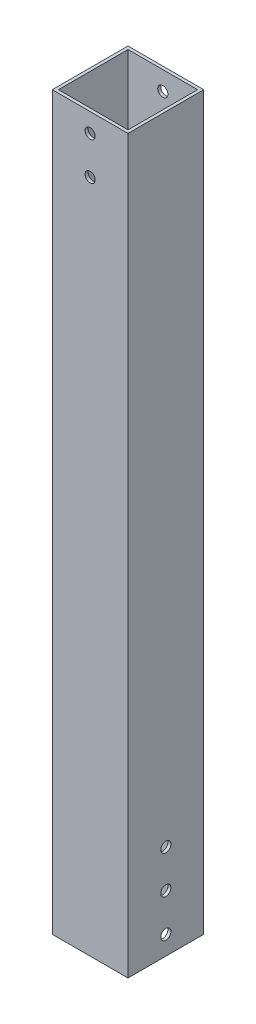
SolidWorks part; units mm, degrees
material "6061 Alloy"
ref_plane "Front Plane" through (0, 0, 0) normal (0, 0, 1) x (1, 0, 0)
ref_plane "Top Plane" through (0, 0, 0) normal (0, 1, 0) x (1, 0, 0)
ref_plane "Right Plane" through (0, 0, 0) normal (1, 0, 0) x (0, 0, -1)
sketch "Sketch1" plane through (0, 0, 0) normal (0, 1, 0) x (1, 0, 0)
  line L1 (19.05, 19.05) -> (-19.05, 19.05)
  line L2 (19.05, 19.05) -> (19.05, -19.05)
  line L3 (19.05, -19.05) -> (-19.05, -19.05)
  line L4 (-19.05, 19.05) -> (-19.05, -19.05)
  line L5 (19.05, 19.05) -> (-19.05, -19.05) construction
  line L6 (19.05, -19.05) -> (-19.05, 19.05) construction
  point P0 (0, 0)
  dimension "D1" = 38.1
extrude "Extrude-Thin1" add sketch "Sketch1" along normal blind 368.3 thin thin type one direction reverse wall 1.524
sketch "Sketch2" plane through (19.05, 0, 0) normal (1, 0, 0) x (0, 0, -1)
  line L0 (-19.05, 0) -> (19.05, 0) construction
  circle A0 centre (0, 9.525) radius 2.54
  circle A1 centre (0, 28.575) radius 2.54
  circle A2 centre (0, 47.625) radius 2.54
  dimension "D1" = 5.08
  dimension "D4" = 19.05
  dimension "D2" = 9.525
  dimension "D3" = 28.575
hole_wizard "#10 Clearance Hole1" positions "Sketch3" profile "Sketch4" hole size "#10" standard "ANSI Inch" end condition through all
sketch "Sketch3" plane through (19.05, 0, 0) normal (1, 0, 0) x (0, 0, -1)
  point P0 (0, 9.525)
  point P3 (0, 28.575)
  point P6 (0, 47.625)
sketch "Sketch4" plane through (19.05, 9.525, 0) normal (0, 1, 0) x (0, 0, -1)
  line L0 (0, 0) -> (0, 38.1)
  line L1 (0, 38.1) -> (2.5527, 38.1)
  line L2 (2.5527, 38.1) -> (2.5527, 0)
  line L5 (2.5527, 0) -> (0, 0)
  line L11 (0, -6.35) -> (0, 107.95) construction
  dimension "Thru Hole Dia." = 5.1054
  dimension "Thru Hole Depth" = 38.1
sketch "Sketch5" plane through (0, 0, 19.05) normal (0, 0, 1) x (1, 0, 0)
  line L0 (-19.05, 368.3) -> (19.05, 368.3) construction
  circle A0 centre (0, 358.775) radius 2.54
  circle A1 centre (0, 339.725) radius 2.54
  dimension "D1" = 5.08
  dimension "D2" = 9.525
  dimension "D3" = 28.575
hole_wizard "#10 Clearance Hole2" positions "Sketch6" profile "Sketch7" hole size "#10" standard "ANSI Inch" end condition through all
sketch "Sketch6" plane through (0, 0, 19.05) normal (0, 0, 1) x (1, 0, 0)
  point P0 (0, 339.725)
  point P3 (0, 358.775)
sketch "Sketch7" plane through (0, 339.725, 19.05) normal (1, 0, 0) x (0, -1, 0)
  line L0 (0, 0) -> (0, 38.1)
  line L1 (0, 38.1) -> (2.5527, 38.1)
  line L2 (2.5527, 38.1) -> (2.5527, 0)
  line L5 (2.5527, 0) -> (0, 0)
  line L11 (0, -6.35) -> (0, 107.95) construction
  dimension "Thru Hole Dia." = 5.1054
  dimension "Thru Hole Depth" = 38.1
sketch "Sketch8" plane through (19.05, 0, 0) normal (1, 0, 0) x (0, 0, -1)
  line L0 (-19.05, 59.7027) -> (19.05, 59.7027) construction
  line L1 (-19.05, 368.3) -> (-19.05, 0) construction
  line L2 (19.05, 368.3) -> (19.05, 0) construction
  line L3 (17.526, 368.3) -> (-17.526, 368.3) construction
  line L4 (-7.7094, 328.6285) -> (6.35, 328.6285) construction
  line L5 (-3.175, 328.6285) -> (3.175, 328.6285)
  line L6 (6.35, 325.4535) -> (6.35, 308.007)
  line L7 (0.1915, 306.9211) -> (-6.1585, 324.3676)
  line L8 (-3.175, 331.8035) -> (3.175, 331.8035)
  line L9 (-6.35, 334.9785) -> (-6.35, 352.425)
  line L10 (-0.1915, 353.5109) -> (6.1585, 336.0644)
  line L11 (-0.1915, 301.9934) -> (6.1585, 284.547)
  line L12 (-6.35, 368.3) -> (-6.35, 0) construction
  line L13 (-19.05, 368.3) -> (19.05, 368.3) construction
  line L14 (-19.05, 0) -> (19.05, 0) construction
  line L15 (6.35, 0) -> (6.35, 368.3) construction
  line L16 (-19.05, 348.6497) -> (-6.35, 348.6497) construction
  line L17 (6.35, 348.6497) -> (19.05, 348.6497) construction
  line L18 (-6.35, 283.461) -> (-6.35, 300.9075)
  line L19 (-3.175, 280.286) -> (3.175, 280.286)
  line L20 (-3.175, 277.111) -> (3.175, 277.111)
  line L21 (0.1915, 255.4036) -> (-6.1585, 272.8501)
  line L22 (6.35, 273.936) -> (6.35, 256.4896)
  line L23 (-0.1915, 250.476) -> (6.1585, 233.0295)
  line L24 (-6.35, 231.9436) -> (-6.35, 249.39)
  line L25 (-3.175, 228.7686) -> (3.175, 228.7686)
  line L26 (-3.175, 225.5936) -> (3.175, 225.5936)
  line L27 (0.1915, 203.8862) -> (-6.1585, 221.3326)
  line L28 (6.35, 222.4186) -> (6.35, 204.9721)
  line L29 (-0.1915, 198.9585) -> (6.1585, 181.512)
  line L30 (-6.35, 180.4261) -> (-6.35, 197.8726)
  line L31 (-3.175, 177.2511) -> (3.175, 177.2511)
  line L32 (-3.175, 174.0761) -> (3.175, 174.0761)
  line L33 (0.1915, 152.3687) -> (-6.1585, 169.8152)
  line L34 (6.35, 170.9011) -> (6.35, 153.4546)
  line L35 (-0.1915, 147.441) -> (6.1585, 129.9945)
  line L36 (-6.35, 128.9086) -> (-6.35, 146.3551)
  line L37 (-3.175, 125.7336) -> (3.175, 125.7336)
  line L38 (-3.175, 122.5586) -> (3.175, 122.5586)
  line L39 (0.1915, 100.8512) -> (-6.1585, 118.2977)
  line L40 (6.35, 119.3836) -> (6.35, 101.9371)
  line L41 (-0.1915, 95.9235) -> (6.1585, 78.477)
  line L42 (-6.35, 77.3911) -> (-6.35, 94.8376)
  line L43 (-3.175, 74.2161) -> (3.175, 74.2161)
  line L47 (6.35, 67.8661) -> (6.35, 50.4196) [skipped]
  line L48 (0.1915, 49.3337) -> (-6.1585, 66.7802) [skipped]
  line L49 (-3.175, 71.0411) -> (3.175, 71.0411) [skipped]
  circle A0 centre (0, 47.625) radius 2.5527 construction
  arc A1 (-6.1585, 324.3676) -> (-3.175, 328.6285) centre (-3.175, 325.4535) cw
  arc A2 (3.175, 328.6285) -> (6.35, 325.4535) centre (3.175, 325.4535) cw
  arc A3 (6.35, 308.007) -> (0.1915, 306.9211) centre (3.175, 308.007) cw
  arc A4 (6.1585, 336.0644) -> (3.175, 331.8035) centre (3.175, 334.9785) cw
  arc A5 (-6.35, 352.425) -> (-0.1915, 353.5109) centre (-3.175, 352.425) cw
  arc A6 (-6.35, 334.9785) -> (-3.175, 331.8035) centre (-3.175, 334.9785) ccw
  arc A7 (-6.35, 300.9075) -> (-0.1915, 301.9934) centre (-3.175, 300.9075) cw
  arc A8 (-6.35, 283.461) -> (-3.175, 280.286) centre (-3.175, 283.461) ccw
  arc A9 (6.1585, 284.547) -> (3.175, 280.286) centre (3.175, 283.461) cw
  arc A10 (-6.1585, 272.8501) -> (-3.175, 277.111) centre (-3.175, 273.936) cw
  arc A11 (6.35, 256.4896) -> (0.1915, 255.4036) centre (3.175, 256.4896) cw
  arc A12 (3.175, 277.111) -> (6.35, 273.936) centre (3.175, 273.936) cw
  arc A13 (-6.35, 249.39) -> (-0.1915, 250.476) centre (-3.175, 249.39) cw
  arc A14 (-6.35, 231.9436) -> (-3.175, 228.7686) centre (-3.175, 231.9436) ccw
  arc A15 (6.1585, 233.0295) -> (3.175, 228.7686) centre (3.175, 231.9436) cw
  arc A16 (-6.1585, 221.3326) -> (-3.175, 225.5936) centre (-3.175, 222.4186) cw
  arc A17 (6.35, 204.9721) -> (0.1915, 203.8862) centre (3.175, 204.9721) cw
  arc A18 (3.175, 225.5936) -> (6.35, 222.4186) centre (3.175, 222.4186) cw
  arc A19 (-6.35, 197.8726) -> (-0.1915, 198.9585) centre (-3.175, 197.8726) cw
  arc A20 (-6.35, 180.4261) -> (-3.175, 177.2511) centre (-3.175, 180.4261) ccw
  arc A21 (6.1585, 181.512) -> (3.175, 177.2511) centre (3.175, 180.4261) cw
  arc A22 (-6.1585, 169.8152) -> (-3.175, 174.0761) centre (-3.175, 170.9011) cw
  arc A23 (6.35, 153.4546) -> (0.1915, 152.3687) centre (3.175, 153.4546) cw
  arc A24 (3.175, 174.0761) -> (6.35, 170.9011) centre (3.175, 170.9011) cw
  arc A25 (-6.35, 146.3551) -> (-0.1915, 147.441) centre (-3.175, 146.3551) cw
  arc A26 (-6.35, 128.9086) -> (-3.175, 125.7336) centre (-3.175, 128.9086) ccw
  arc A27 (6.1585, 129.9945) -> (3.175, 125.7336) centre (3.175, 128.9086) cw
  arc A28 (-6.1585, 118.2977) -> (-3.175, 122.5586) centre (-3.175, 119.3836) cw
  arc A29 (6.35, 101.9371) -> (0.1915, 100.8512) centre (3.175, 101.9371) cw
  arc A30 (3.175, 122.5586) -> (6.35, 119.3836) centre (3.175, 119.3836) cw
  arc A31 (-6.35, 94.8376) -> (-0.1915, 95.9235) centre (-3.175, 94.8376) cw
  arc A32 (-6.35, 77.3911) -> (-3.175, 74.2161) centre (-3.175, 77.3911) ccw
  arc A33 (6.1585, 78.477) -> (3.175, 74.2161) centre (3.175, 77.3911) cw
  arc A37 (6.35, 50.4196) -> (0.1915, 49.3337) centre (3.175, 50.4196) cw [skipped]
  arc A38 (3.175, 71.0411) -> (6.35, 67.8661) centre (3.175, 67.8661) cw [skipped]
  arc A39 (-6.1585, 66.7802) -> (-3.175, 71.0411) centre (-3.175, 67.8661) cw [skipped]
  dimension "D1" = 9.525
  dimension "D3" = 3.175
  dimension "D5" = 15.875
  dimension "D8" = 3.175
  dimension "D2" = 20
  dimension "D4" = 12.7
  dimension "D6" = 3.175
  dimension "D7" = 6
extrude "Cut-Extrude1" [suppressed] cut sketch "Sketch8" against normal through all
sketch "Sketch9" plane through (0, 0, 19.05) normal (0, 0, 1) x (1, 0, 0)
  line L0 (-7.7094, 330.2) -> (6.35, 330.2) construction
  line L1 (-3.175, 330.2) -> (3.175, 330.2)
  line L2 (6.35, 327.025) -> (6.35, 309.5785)
  line L3 (0.1915, 308.4926) -> (-6.1585, 325.9391)
  line L4 (-3.175, 281.8575) -> (3.175, 281.8575)
  line L5 (-6.35, 285.0325) -> (-6.35, 302.479)
  line L6 (-0.1915, 303.5649) -> (6.1585, 286.1184)
  line L7 (-3.175, 278.6825) -> (3.175, 278.6825)
  line L8 (-6.35, 368.3) -> (-6.35, 0) construction
  line L9 (-19.05, 368.3) -> (19.05, 368.3) construction
  line L10 (-19.05, 0) -> (19.05, 0) construction
  line L11 (6.35, 0) -> (6.35, 368.3) construction
  line L12 (-19.05, 360.2771) -> (-6.35, 360.2771) construction
  line L13 (-19.05, 368.3) -> (-19.05, 0) construction
  line L14 (6.35, 360.2771) -> (19.05, 360.2771) construction
  line L15 (19.05, 368.3) -> (19.05, 0) construction
  line L16 (0.1915, 256.9751) -> (-6.1585, 274.4216)
  line L17 (6.35, 275.5075) -> (6.35, 258.061)
  line L18 (-6.35, 233.515) -> (-6.35, 250.9615)
  line L19 (-0.1915, 252.0474) -> (6.1585, 234.601)
  line L20 (-3.175, 230.34) -> (3.175, 230.34)
  line L21 (-3.175, 227.165) -> (3.175, 227.165)
  line L22 (0.1915, 205.4576) -> (-6.1585, 222.9041)
  line L23 (6.35, 223.99) -> (6.35, 206.5436)
  line L24 (-6.35, 181.9976) -> (-6.35, 199.444)
  line L25 (-0.1915, 200.53) -> (6.1585, 183.0835)
  line L26 (-3.175, 178.8226) -> (3.175, 178.8226)
  line L27 (-3.175, 175.6476) -> (3.175, 175.6476)
  line L28 (0.1915, 153.9402) -> (-6.1585, 171.3866)
  line L29 (6.35, 172.4726) -> (6.35, 155.0261)
  line L30 (-6.35, 130.4801) -> (-6.35, 147.9266)
  line L31 (-0.1915, 149.0125) -> (6.1585, 131.566)
  line L32 (-3.175, 127.3051) -> (3.175, 127.3051)
  line L33 (-3.175, 124.1301) -> (3.175, 124.1301)
  line L34 (0.1915, 102.4227) -> (-6.1585, 119.8692)
  line L35 (6.35, 120.9551) -> (6.35, 103.5086)
  line L36 (-6.35, 78.9626) -> (-6.35, 96.4091)
  line L37 (-0.1915, 97.495) -> (6.1585, 80.0485)
  line L38 (-3.175, 75.7876) -> (3.175, 75.7876)
  line L39 (-3.175, 72.6126) -> (3.175, 72.6126)
  line L40 (0.1915, 50.9052) -> (-6.1585, 68.3517)
  line L41 (6.35, 69.4376) -> (6.35, 51.9911)
  line L42 (-6.35, 27.4451) -> (-6.35, 44.8916)
  line L43 (-0.1915, 45.9775) -> (6.1585, 28.531)
  line L44 (-3.175, 24.2701) -> (3.175, 24.2701)
  arc A0 (-6.1585, 325.9391) -> (-3.175, 330.2) centre (-3.175, 327.025) cw
  arc A1 (3.175, 330.2) -> (6.35, 327.025) centre (3.175, 327.025) cw
  arc A2 (6.35, 309.5785) -> (0.1915, 308.4926) centre (3.175, 309.5785) cw
  arc A3 (6.1585, 286.1184) -> (3.175, 281.8575) centre (3.175, 285.0325) cw
  arc A4 (-6.35, 302.479) -> (-0.1915, 303.5649) centre (-3.175, 302.479) cw
  arc A5 (-6.35, 285.0325) -> (-3.175, 281.8575) centre (-3.175, 285.0325) ccw
  circle A6 centre (0, 339.725) radius 2.5527 construction
  arc A7 (-6.1585, 274.4216) -> (-3.175, 278.6825) centre (-3.175, 275.5075) cw
  arc A8 (3.175, 278.6825) -> (6.35, 275.5075) centre (3.175, 275.5075) cw
  arc A9 (6.35, 258.061) -> (0.1915, 256.9751) centre (3.175, 258.061) cw
  arc A10 (-6.35, 250.9615) -> (-0.1915, 252.0474) centre (-3.175, 250.9615) cw
  arc A11 (6.1585, 234.601) -> (3.175, 230.34) centre (3.175, 233.515) cw
  arc A12 (-6.35, 233.515) -> (-3.175, 230.34) centre (-3.175, 233.515) ccw
  arc A13 (-6.1585, 222.9041) -> (-3.175, 227.165) centre (-3.175, 223.99) cw
  arc A14 (3.175, 227.165) -> (6.35, 223.99) centre (3.175, 223.99) cw
  arc A15 (6.35, 206.5436) -> (0.1915, 205.4576) centre (3.175, 206.5436) cw
  arc A16 (-6.35, 199.444) -> (-0.1915, 200.53) centre (-3.175, 199.444) cw
  arc A17 (6.1585, 183.0835) -> (3.175, 178.8226) centre (3.175, 181.9976) cw
  arc A18 (-6.35, 181.9976) -> (-3.175, 178.8226) centre (-3.175, 181.9976) ccw
  arc A19 (-6.1585, 171.3866) -> (-3.175, 175.6476) centre (-3.175, 172.4726) cw
  arc A20 (3.175, 175.6476) -> (6.35, 172.4726) centre (3.175, 172.4726) cw
  arc A21 (6.35, 155.0261) -> (0.1915, 153.9402) centre (3.175, 155.0261) cw
  arc A22 (-6.35, 147.9266) -> (-0.1915, 149.0125) centre (-3.175, 147.9266) cw
  arc A23 (6.1585, 131.566) -> (3.175, 127.3051) centre (3.175, 130.4801) cw
  arc A24 (-6.35, 130.4801) -> (-3.175, 127.3051) centre (-3.175, 130.4801) ccw
  arc A25 (-6.1585, 119.8692) -> (-3.175, 124.1301) centre (-3.175, 120.9551) cw
  arc A26 (3.175, 124.1301) -> (6.35, 120.9551) centre (3.175, 120.9551) cw
  arc A27 (6.35, 103.5086) -> (0.1915, 102.4227) centre (3.175, 103.5086) cw
  arc A28 (-6.35, 96.4091) -> (-0.1915, 97.495) centre (-3.175, 96.4091) cw
  arc A29 (6.1585, 80.0485) -> (3.175, 75.7876) centre (3.175, 78.9626) cw
  arc A30 (-6.35, 78.9626) -> (-3.175, 75.7876) centre (-3.175, 78.9626) ccw
  arc A31 (-6.1585, 68.3517) -> (-3.175, 72.6126) centre (-3.175, 69.4376) cw
  arc A32 (3.175, 72.6126) -> (6.35, 69.4376) centre (3.175, 69.4376) cw
  arc A33 (6.35, 51.9911) -> (0.1915, 50.9052) centre (3.175, 51.9911) cw
  arc A34 (-6.35, 44.8916) -> (-0.1915, 45.9775) centre (-3.175, 44.8916) cw
  arc A35 (6.1585, 28.531) -> (3.175, 24.2701) centre (3.175, 27.4451) cw
  arc A36 (-6.35, 27.4451) -> (-3.175, 24.2701) centre (-3.175, 27.4451) ccw
  dimension "D2" = 3.175
  dimension "D4" = 3.175
  dimension "D1" = 20
  dimension "D3" = 12.7
  dimension "D5" = 9.525
  dimension "D7" = 3.175
  dimension "D6" = 6
extrude "Cut-Extrude2" [suppressed] cut sketch "Sketch9" against normal through all
